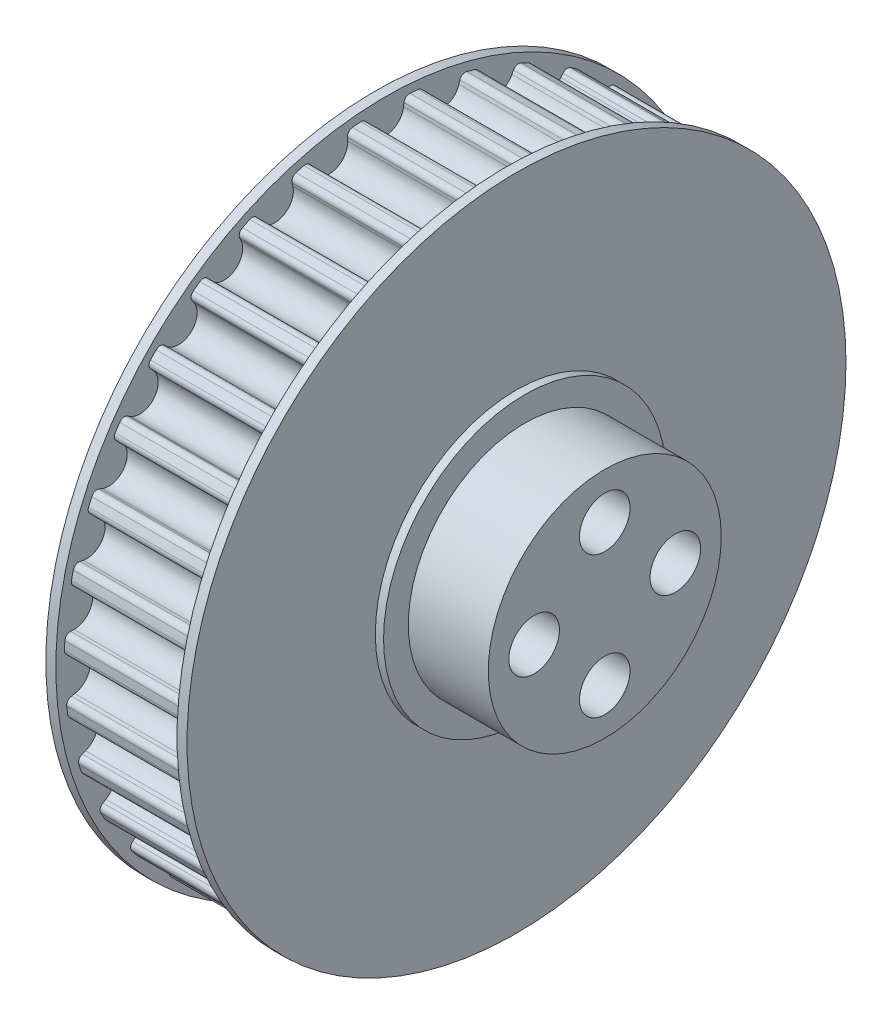
SolidWorks part; units mm, degrees
material "ABS"
ref_plane "前视基准面" through (0, 0, 0) normal (0, 0, 1) x (1, 0, 0)
ref_plane "上视基准面" through (0, 0, 0) normal (0, 1, 0) x (1, 0, 0)
ref_plane "右视基准面" through (0, 0, 0) normal (1, 0, 0) x (0, 0, -1)
sketch "草图1" plane through (0, 0, 0) normal (0, 0, 1) x (1, 0, 0)
  line L0 (0, 0) -> (64.8368, 0) construction
  line L1 (0, 0) -> (0, 27.278)
  line L2 (0, 27.278) -> (10.3, 27.278)
  line L3 (10.3, 27.278) -> (10.3, 0)
  line L6 (10.3, 0) -> (0, 0)
  dimension "B" = 10.3
  dimension "da" = 54.556
revolve "旋转1" add sketch "草图1" angle 360 about L0
ref_axis "基准轴1" through (-1, 0, 0) along (1, 0, 0)
sketch "草图6" plane through (0, 0, 0) normal (1, 0, 0) x (0, 0, -1)
  line L0 (0, 0) -> (0, 30.6512) construction
  line L1 (1.5839, 26.7772) -> (1.5484, 26.4879)
  line L2 (2.5954, 27.1543) -> (2.792, 28.7558)
  line L3 (-2.5954, 27.1543) -> (-2.792, 28.7558)
  line L4 (-1.5839, 26.7772) -> (-1.5484, 26.4879)
  circle A0 centre (0, 0) radius 27.278 construction
  circle A1 centre (0, 0) radius 25.118 construction
  arc A2 (-1.5484, 26.4879) -> (1.5484, 26.4879) centre (0, 26.678) ccw
  arc A3 (2.792, 28.7558) -> (-2.792, 28.7558) centre (0, 0) ccw
  arc A4 (1.5839, 26.7772) -> (2.0972, 27.1973) centre (2.0603, 26.7187) cw
  arc A5 (2.0972, 27.1973) -> (2.5954, 27.1543) centre (0, 0) cw
  arc A6 (-2.0972, 27.1973) -> (-2.5954, 27.1543) centre (0, 0) ccw
  arc A7 (-1.5839, 26.7772) -> (-2.0972, 27.1973) centre (-2.0603, 26.7187) ccw
  circle A8 centre (0, 0) radius 27.278 construction
  point P7 (0, 3.25)
  point P8 (0, 28.4912)
  point P15 (1.6393, 27.2287)
  dimension "ra" = 0.48
  dimension "rf" = 1.56
  dimension "hg" = 2.16
  dimension "D3" = 0.5
  dimension "D4" = 1.6136
  dimension "angle" = 14
  dimension "bw" = 3.25
  dimension "D1" = 2.16
extrude "切除-拉伸2" cut sketch "草图6" along normal up to next
pattern_circular "阵列(圆周)3" count 35 over 360 about axis through (-1, 0, 0) along (1, 0, 0) of "切除-拉伸2"
sketch "草图7" plane through (10.3, 0, 0) normal (1, 0, 0) x (0, 0, -1)
  circle A0 centre (0, 0) radius 28
  dimension "D1" = 56
extrude "凸台-拉伸1" add sketch "草图7" along normal blind 0.85
sketch "草图8" plane through (11.15, 0, 0) normal (1, 0, 0) x (0, 0, -1)
  circle A0 centre (0, 0) radius 12
  dimension "D1" = 24
extrude "凸台-拉伸2" add sketch "草图8" along normal blind 0.7
sketch "草图9" plane through (11.85, 0, 0) normal (1, 0, 0) x (0, 0, -1)
  circle A0 centre (0, 0) radius 9.9
  dimension "D1" = 19.8
extrude "凸台-拉伸3" add sketch "草图9" along normal blind 6.8
ref_plane "基准面1" through (5.15, 0, 0) normal (-1, 0, 0) x (0, 0, 1)
mirror "镜向1" about plane through (5.15, 0, 0) normal (-1, 0, 0) of "凸台-拉伸3", "凸台-拉伸2", "凸台-拉伸1"
sketch "草图10" plane through (18.65, 0, 0) normal (1, 0, 0) x (0, 0, -1)
  circle A0 centre (0, 0) radius 6 construction
  circle A1 centre (0, 6) radius 2.15
  circle A2 centre (6, 0) radius 2.15
  circle A3 centre (0, -6) radius 2.15
  circle A4 centre (-6, 0) radius 2.15
  dimension "D1" = 12
  dimension "D2" = 4.3
  dimension "D3" = 4
extrude "切除-拉伸3" cut sketch "草图10" against normal through all
equation "\"D3@草图6\" = \"ra@草图6\""
